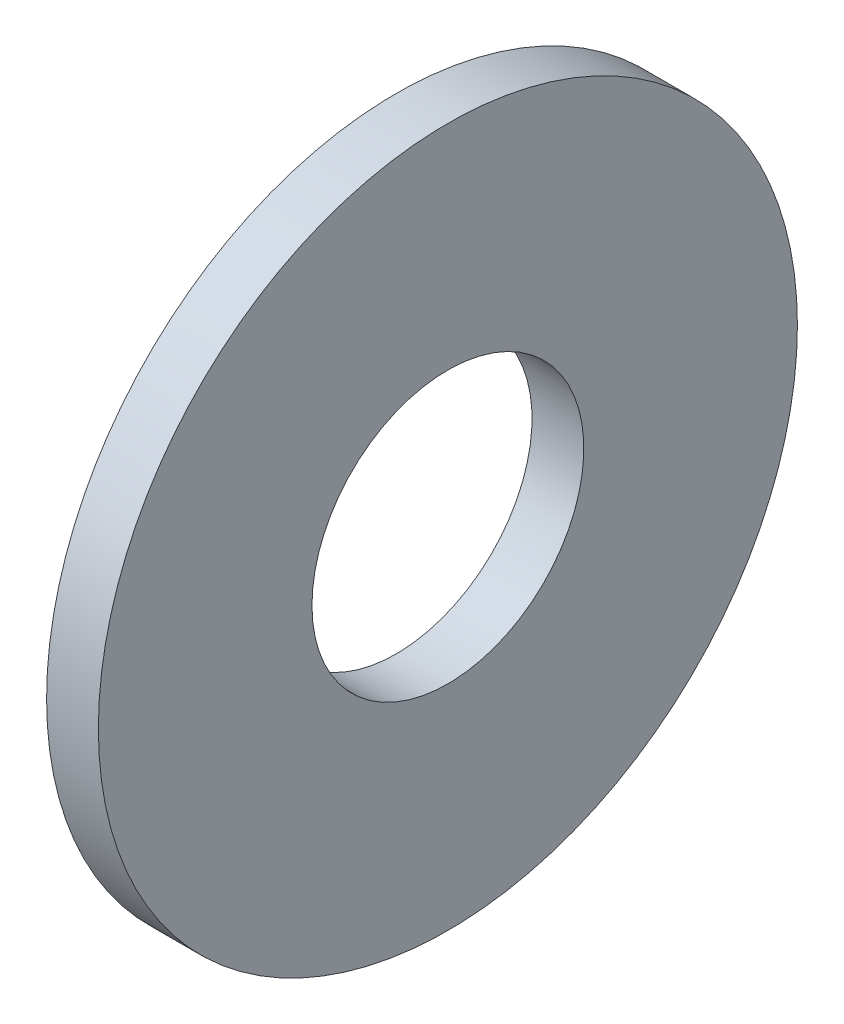
SolidWorks part; units mm, degrees
ref_plane "Plan1" through (0, 0, 0) normal (0, 0, 1) x (1, 0, 0)
ref_plane "Plan2" through (0, 0, 0) normal (0, 1, 0) x (1, 0, 0)
ref_plane "Plan3" through (0, 0, 0) normal (1, 0, 0) x (0, 0, -1)
sketch "Esquisse1" plane through (0, 0, 0) normal (0, 1, 0) x (1, 0, 0)
  line L0 (0, 0) -> (40, 0) construction
  line L2 (0, 13.5) -> (2, 13.5)
  line L3 (0, 13.5) -> (0, 5.25)
  line L4 (0, 5.25) -> (2, 5.25)
  line L5 (2, 13.5) -> (2, 5.25)
  dimension "D1" = 5.25
  dimension "D2" = 13.5
  dimension "D3" = 2
revolve "Base-Révolution" add sketch "Esquisse1" angle 360 about L0
ref_axis "Axe1" through (-50, 0, 0) along (1, 0, 0)
